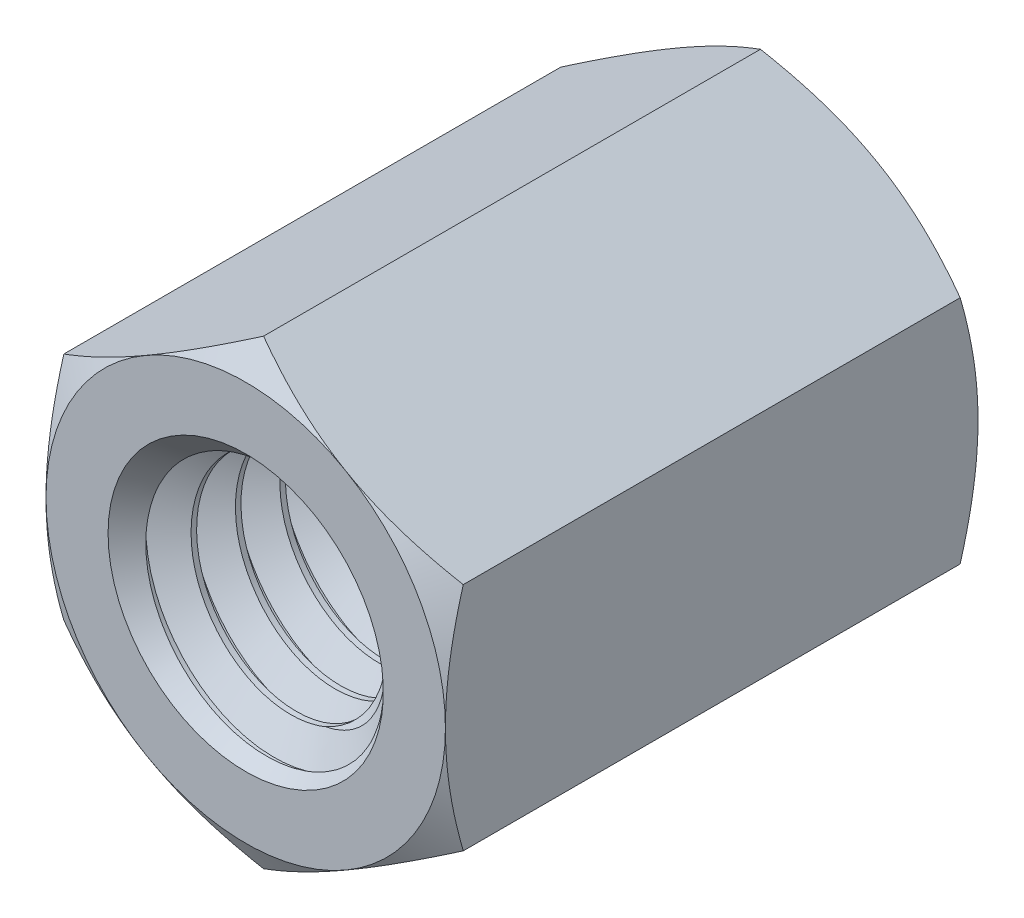
SolidWorks part; units mm, degrees
ref_plane "Front Plane" through (0, 0, 0) normal (0, 0, 1) x (1, 0, 0)
ref_plane "Top Plane" through (0, 0, 0) normal (0, 1, 0) x (1, 0, 0)
ref_plane "Right Plane" through (0, 0, 0) normal (1, 0, 0) x (0, 0, -1)
sketch "Sketch3" plane through (0, 0, 0) normal (1, 0, 0) x (0, 0, -1)
  line L0 (-3, 0) -> (3, 0) construction
  line L1 (0, 2.25) -> (0, -2.25) construction
  line L2 (-3, 1.5) -> (-3, -1.5) construction
  point P2 (-1.8, 0)
  point P3 (1.8, 0)
  dimension "D1" = 4.8
  dimension "Length" = 6
  dimension "Min Thread Length" = 4.8
  dimension "Thread Dia" = 3
  dimension "Hex" = 4.5
sketch "Sketch1" plane through (0, 0, 0) normal (0, 0, 1) x (1, 0, 0)
  line L1 (0, 2.5981) -> (-2.25, 1.299)
  line L2 (-2.25, 1.299) -> (-2.25, -1.299)
  line L3 (-2.25, -1.299) -> (0, -2.5981)
  line L4 (0, -2.5981) -> (2.25, -1.299)
  line L5 (2.25, -1.299) -> (2.25, 1.299)
  line L6 (2.25, 1.299) -> (0, 2.5981)
  circle A0 centre (0, 0) radius 2.25 construction
  circle A1 centre (0, 0) radius 1.5
extrude "Extrude1" add sketch "Sketch1" along normal up to vertex (3 mm away) and the other way up to vertex (3 mm away) up to point (0, 0, 3) other way up to point (0, 0, -3)
sketch "Sketch11" plane through (0, 0, -3) normal (0, 0, -1) x (-1, 0, 0)
  circle A0 centre (0, 0) radius 1.5 construction
  circle A1 centre (0, 0) radius 1.5
curve "Helix/Spiral1" pitch 0.5 height 6.5 radius 1.5 centre (0, 0, -3) axis (0, 0, 1) start towards (0, 1, 0) parameters "Pitch"=0.5
sketch "Sketch12" plane through (0, 0, 0) normal (1, 0, 0) x (0, 0, -1)
  line L0 (3.4375, 1.5) -> (3, 1.5)
  line L1 (3.4375, 1.5) -> (3.25, 1.1752)
  line L2 (3.25, 1.1752) -> (3.1875, 1.1752)
  line L3 (3.1875, 1.1752) -> (3, 1.5)
  line L4 (3.2187, 1.1752) -> (3.2187, 1.5) construction
  line L5 (3.3438, 1.3376) -> (3.0938, 1.3376) construction
  dimension "D1" = 0.0625
  dimension "D2" = 0.25
  dimension "D3" = 60
sweep "Sweep1" add profiles "Sketch12" path "Helix/Spiral1"
sketch "Sketch6" plane through (0, 0, -3) normal (0, 0, -1) x (-1, 0, 0)
  line L6 (0, 2.5981) -> (-2.25, 1.299)
  line L7 (-2.25, 1.299) -> (-2.25, -1.299)
  line L8 (-2.25, -1.299) -> (0, -2.5981)
  line L9 (0, -2.5981) -> (2.25, -1.299)
  line L10 (2.25, -1.299) -> (2.25, 1.299)
  line L11 (2.25, 1.299) -> (0, 2.5981)
  line L12 (0, 2.5981) -> (-2.25, 1.299)
  line L13 (-2.25, 1.299) -> (-2.25, -1.299)
  line L14 (-2.25, -1.299) -> (0, -2.5981)
  line L15 (0, -2.5981) -> (2.25, -1.299)
  line L16 (2.25, -1.299) -> (2.25, 1.299)
  line L17 (2.25, 1.299) -> (0, 2.5981)
  dimension "D1" = 0
extrude "Extrude2" cut sketch "Sketch6" along normal through all
sketch "Sketch7" plane through (0, 0, -3) normal (0, 0, -1) x (-1, 0, 0)
  circle A2 centre (0, 0) radius 1.5508
  circle A3 centre (0, 0) radius 1.5508
  dimension "D1" = 0.0508
extrude "Extrude3" cut sketch "Sketch7" against normal through all draft 43
sketch "Sketch8" plane through (0, 0, -3) normal (0, 0, -1) x (-1, 0, 0)
  circle A0 centre (0, 0) radius 2.25 construction
  circle A1 centre (0, 0) radius 2.25
extrude "Extrude4" cut sketch "Sketch8" against normal through all draft 60 flip side to cut
mirror "Mirror1" about plane through (0, 0, 0) normal (0, 0, 1) of "Extrude2", "Extrude3", "Extrude4"
sketch "Sketch9" [suppressed] plane through (0, 0, 0) normal (1, 0, 0) x (0, 0, -1)
  line L1 (-1.2, 1.1353) -> (1.2, 1.1353)
  line L2 (-1.2, 1.1353) -> (-1.2, 0)
  line L3 (-1.2, 0) -> (1.2, 0)
  line L4 (1.2, 1.1353) -> (1.2, 0)
  line L7 (-6, 0) -> (6, 0) construction
revolve "Revolve" [suppressed] add sketch "Sketch9" angle 360 about L0
sketch "Sketch10" [suppressed] plane through (0, 0, 0) normal (1, 0, 0) x (0, 0, -1)
  line L0 (6, 1.25) -> (1.2, 1.25)
  line L1 (-6, 1.25) -> (-1.2, 1.25)
  line L2 (1.2, 1.25) -> (1.2, -1.25)
  line L3 (-6, -1.25) -> (-1.2, -1.25)
  line L4 (-1.2, 1.25) -> (-1.2, -1.25)
  line L5 (1.2, -1.25) -> (6, -1.25)
equation "\"D1@Sketch3\" = \"Min Thread Length@Sketch3\""
equation "\"D3@Helix/Spiral1\" = \"Length@Sketch3\"+\"Pitch@Helix/Spiral1\""
equation "\"D1@Sketch12\" = \"Pitch@Helix/Spiral1\"*.125"
equation "\"D2@Sketch12\" = \"Pitch@Helix/Spiral1\"*.5"
